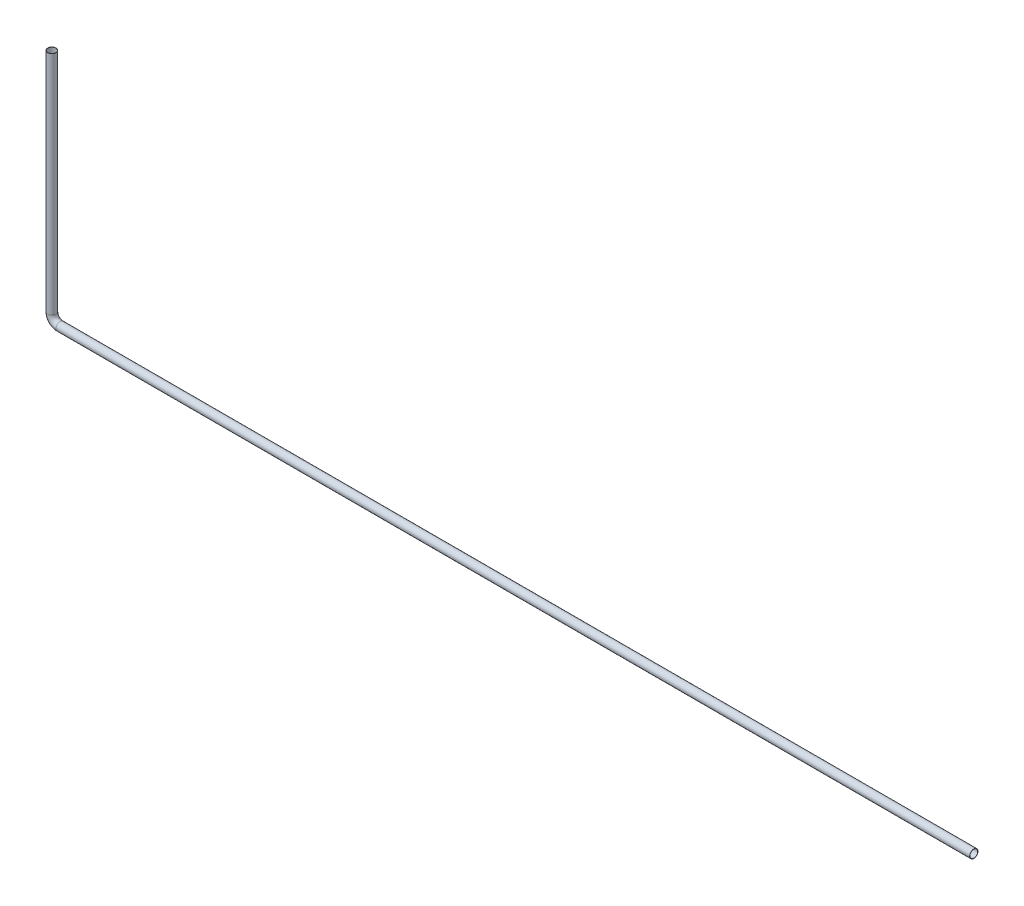
SolidWorks part; units mm, degrees
ref_plane "Plano frontal" through (0, 0, 0) normal (0, 0, 1) x (1, 0, 0)
ref_plane "Plano superior" through (0, 0, 0) normal (0, 1, 0) x (1, 0, 0)
ref_plane "Plano direito" through (0, 0, 0) normal (1, 0, 0) x (0, 0, -1)
sketch3d "3DSketch1"
  line L0 (-31937.4493, -17298.2109, 41543.1604) -> (-31937.4493, -17298.2109, 41084.0667) construction
  line L1 (-31937.4493, -17298.2109, 41543.1604) -> (-31937.4493, -17298.2109, 39237.3639) construction
  line L3 (-31937.4493, -17211.1784, 41573.1604) -> (-31937.4493, -18029.1718, 41573.1604)
  line L4 (-31907.4493, -18059.1718, 41573.1604) -> (-28606.3297, -18059.1718, 41573.1604)
  arc A0 (-31907.4493, -18059.1718, 41573.1604) -> (-31937.4493, -18029.1718, 41573.1604) centre (-31907.4493, -18029.1718, 41573.1604) ccw
  point P5 (0, 0, 0)
  point P8 (-28616.3297, -18905.1444, 42044.3544)
  point P12 (-31937.4493, -18059.1718, 41573.1604)
  point P13 (-31907.4493, -18029.1718, 41543.1604)
  point P15 (0, 0, 0)
  point P16 (-31937.4493, -17581.1784, 41573.1604)
  point P17 (0, 0, 0)
  point P19 (0, 0, 0)
  dimension "D1" = 30
sweep "Sweep-Thin1" add path "3DSketch1" circular profile diameter 30 parameters "D1"=1, "D3"=30
